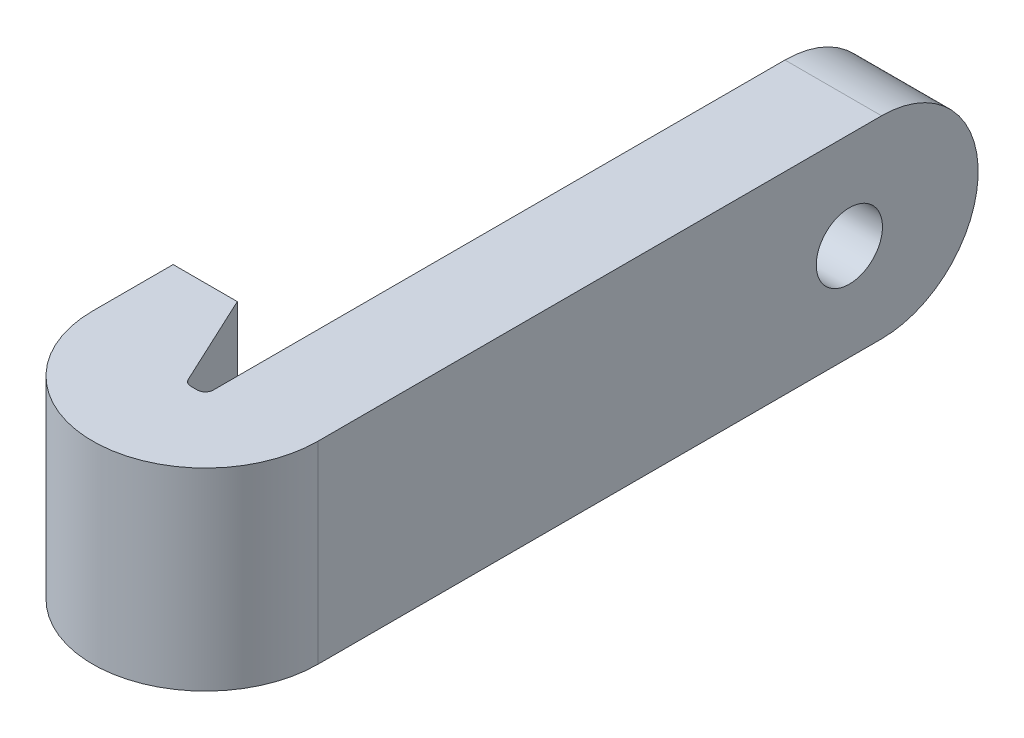
SolidWorks part; units mm, degrees
material "Polycarbonate"
ref_plane "Front Plane" through (0, 0, 0) normal (0, 0, 1) x (1, 0, 0)
ref_plane "Top Plane" through (0, 0, 0) normal (0, 1, 0) x (1, 0, 0)
ref_plane "Right Plane" through (0, 0, 0) normal (1, 0, 0) x (0, 0, -1)
sketch "Sketch1" plane through (0, 0, 0) normal (0, 1, 0) x (1, 0, 0)
  line L0 (0, 0) -> (-7.9375, 0)
  line L13 (0, 0) -> (3.175, 0)
  line L14 (-1.5875, 4.7625) -> (-1.5875, 38.1)
  line L15 (-1.5875, 38.1) -> (3.175, 38.1)
  line L16 (3.175, 0) -> (3.175, 38.1)
  line L17 (-7.9375, 0) -> (-7.9375, 9.525)
  line L18 (-7.9375, 9.525) -> (-4.7735, 9.525)
  line L19 (-4.7735, 9.525) -> (-2.5527, 4.7625)
  line L20 (-2.5527, 4.7625) -> (-1.5875, 4.7625)
  dimension "D1" = 4.7625
  dimension "D2" = 6.35
  dimension "D3" = 9.525
  dimension "D4" = 25
  dimension "D5" = 4.7625
  dimension "D6" = 0.9652
  dimension "D8" = 38.1
extrude "Boss-Extrude1" add sketch "Sketch1" along normal blind 9.525
fillet "Fillet1" radius 0.3969 2 edges at (-2.5527, 4.7625, -4.7625) (-1.5875, 4.7625, -4.7625)
fillet "Fillet3" 2 edges at (-7.9375, 4.7625, 0) (3.175, 4.7625, 0) type full round first side face at (-7.9375, 4.7625, -4.7625) second side face at (3.175, 4.7625, -19.05) middle face at (-2.3812, 4.7625, 0)
fillet "Fillet4" 2 edges at (0.7938, 0, -38.1) (0.7938, 9.525, -38.1) type full round first side face at (-2.4368, 0, -12.0348) second side face at (-2.4368, 9.525, -12.0348) middle face at (0.7938, 4.7625, -38.1)
hole_wizard "#4 Clearance Hole1" positions "Sketch2" profile "Sketch3" hole size "#4" standard "ANSI Inch" end condition through all
sketch "Sketch2" plane through (3.175, 0, 0) normal (1, 0, 0) x (0, 0, -1)
  arc A0 (33.3375, 0) -> (33.3375, 9.525) centre (33.3375, 4.7625) ccw construction
  point P0 (31.75, 4.7625)
  point P6 (38.1, 4.7625)
  dimension "D1" = 6.35
sketch "Sketch3" plane through (3.175, 4.7625, -31.75) normal (0, 1, 0) x (0, 0, -1)
  line L0 (0, 0) -> (0, 11.1125)
  line L1 (0, 11.1125) -> (1.6319, 11.1125)
  line L2 (1.6319, 11.1125) -> (1.6319, 0)
  line L5 (1.6319, 0) -> (0, 0)
  line L11 (0, -6.35) -> (0, 107.95) construction
  dimension "Thru Hole Dia." = 3.2639
  dimension "Thru Hole Depth" = 11.1125
